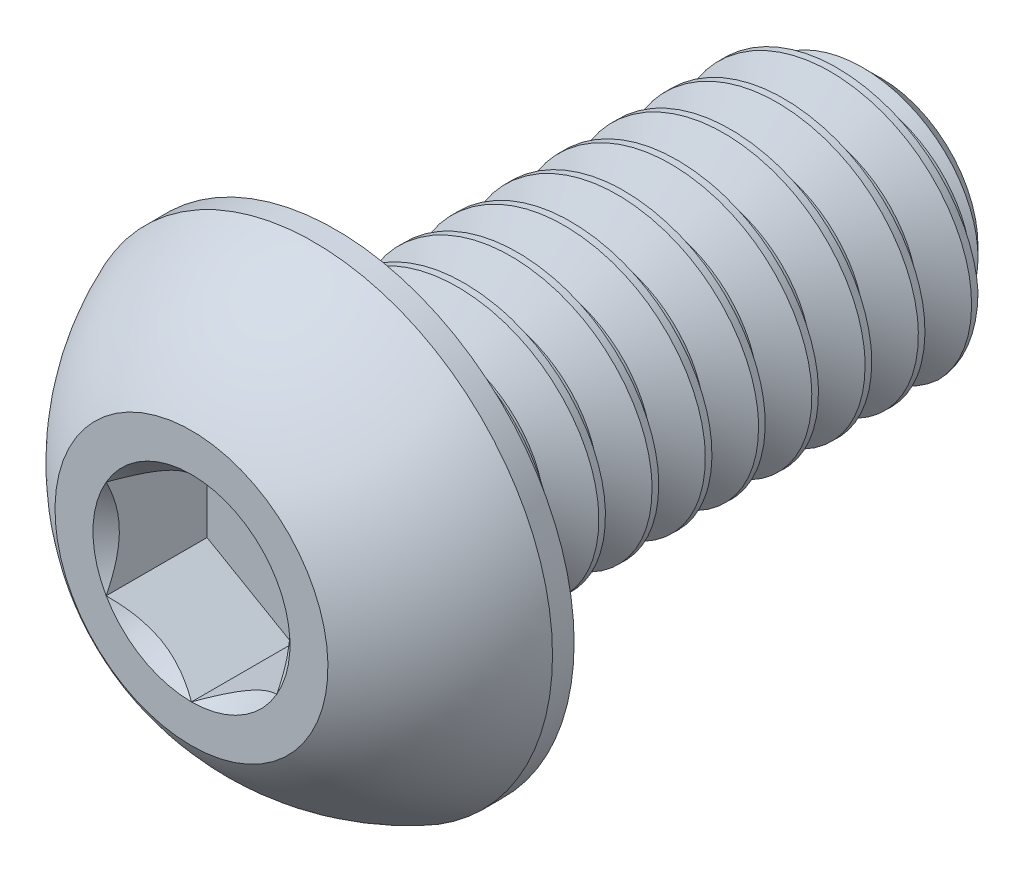
SolidWorks part; units mm, degrees
ref_plane "Front" through (0, 0, 0) normal (0, 0, 1) x (1, 0, 0)
ref_plane "Top" through (0, 0, 0) normal (0, 1, 0) x (1, 0, 0)
ref_plane "Right" through (0, 0, 0) normal (1, 0, 0) x (0, 0, -1)
sketch "Sketch1" plane through (0, 0, 0) normal (1, 0, 0) x (0, 0, -1)
  line L2 (3.3528, 3.175) -> (16.0528, 3.175)
  line L3 (16.0528, 3.175) -> (16.0528, 0)
  line L4 (16.0528, 0) -> (3.3528, 0)
  line L6 (2.8499, 5.5499) -> (3.3528, 5.5499) construction
  line L7 (16.0528, 3.175) -> (16.0528, -3.175) construction
  line L8 (0, 0) -> (3.3528, 0) construction
  line L9 (3.3528, 5.5499) -> (3.3528, -5.5499) construction
  line L11 (3.3528, 3.175) -> (3.3528, 0)
  line L13 (0, 1.9844) -> (0, -1.9844) construction
  line L14 (0, 1.9844) -> (0, 3.175) construction
  arc A3 (0, 3.175) -> (2.8499, 5.5499) centre (5.0603, 0) cw construction
  dimension "D1" = 0.5029
  dimension "Head Ht" = 3.3528
  dimension "Head Dia" = 11.0998
  dimension "Dia" = 6.35
  dimension "Lg" = 12.7
  dimension "Hex" = 3.9688
revolve "Revolve1" add sketch "Sketch1" angle 360 mid plane about L4
sketch "Sketch3" plane through (0, 0, -16.0528) normal (0, 0, -1) x (-1, 0, 0)
  circle A0 centre (0, 0) radius 3.175
curve "Helix/Spiral1" pitch 1.239 height 16.0528 radius 3.175 centre (0, 0, -16.0528) axis (0, 0, 1) start towards (0, 1, 0)
sketch "Sketch2" plane through (0, 0, 0) normal (1, 0, 0) x (0, 0, -1)
  line L0 (16.0528, 3.175) -> (17.1369, 3.175)
  line L1 (17.1369, 3.175) -> (16.6723, 2.3702)
  line L2 (16.6723, 2.3702) -> (16.5174, 2.3702)
  line L3 (16.5174, 2.3702) -> (16.0528, 3.175)
  line L4 (16.2851, 2.7726) -> (16.9046, 2.7726) construction
  dimension "D1" = 60
  dimension "D2" = 0.1549
  dimension "D3" = 0.6195
chamfer "Chamfer1" distance 0.9293 angle 45 1 edges at (0, 3.175, -16.0528)
sweep "Cut-Sweep1" cut profiles "Sketch2" path "Helix/Spiral1"
sketch "Sketch7" plane through (0, 0, 0) normal (1, 0, 0) x (0, 0, -1)
  line L6 (2.8499, 5.5499) -> (3.3528, 5.5499) construction
  line L8 (0, 0) -> (3.3528, 0) construction
  line L11 (3.3528, 5.5499) -> (3.3528, -5.5499) construction
  line L12 (2.8499, 5.5499) -> (3.3528, 5.5499)
  line L13 (0, 0) -> (3.3528, 0)
  line L14 (0, 1.9844) -> (0, -1.9844) construction
  line L15 (3.3528, 5.5499) -> (3.3528, 0)
  line L16 (0, 3.175) -> (0, 0)
  arc A2 (2.8499, 5.5499) -> (0, 3.175) centre (5.0603, 0) ccw construction
  arc A3 (2.8499, 5.5499) -> (0, 3.175) centre (5.0603, 0) ccw
revolve "Revolve2" add sketch "Sketch7" angle 360 mid plane about L13
sketch "Sketch5" plane through (0, 0, 0) normal (0, 0, 1) x (1, 0, 0)
  line L1 (1.9844, -1.1457) -> (1.9844, 1.1457)
  line L2 (1.9844, 1.1457) -> (0, 2.2914)
  line L3 (0, 2.2914) -> (-1.9844, 1.1457)
  line L4 (-1.9844, 1.1457) -> (-1.9844, -1.1457)
  line L5 (-1.9844, -1.1457) -> (0, -2.2914)
  line L6 (0, -2.2914) -> (1.9844, -1.1457)
  circle A0 centre (0, 0) radius 1.9844 construction
extrude "Cut-Extrude2" cut sketch "Sketch5" against normal blind 2.347
sketch "Sketch6" plane through (0, 0, 0) normal (0, 0, 1) x (1, 0, 0)
  circle A0 centre (0, 0) radius 2.2914
extrude "Cut-Extrude3" cut sketch "Sketch6" against normal blind 2.347 draft 45
sketch "Sketch9" [suppressed] plane through (0, 0, -3.3528) normal (0, 0, 1) x (1, 0, 0)
  circle A2 centre (0, 0) radius 3.175
extrude "Boss-Extrude2" [suppressed] add sketch "Sketch9" against normal offset from surface (76.2 mm away) 22.225 up to face at (0, 2.2457, -16.0528)
sketch "Sketch10" plane through (0, 0, 0) normal (1, 0, 0) x (0, 0, -1)
  line L0 (16.0528, 3.175) -> (16.0528, -3.175) construction
  point P0 (14.1943, -3.175)
  dimension "D1" = 1.8585
equation "\"D3@Helix/Spiral1\" = \"Lg@Sketch1\" + \"Head Ht@Sketch1\""
equation "\"D2@Sketch2\" = \"D4@Helix/Spiral1\" * .125"
equation "\"D3@Sketch2\" = \"D4@Helix/Spiral1\" * .5"
equation "\"D1@Chamfer1\" = \"D4@Helix/Spiral1\" * .75"
equation "\"D1@Cut-Extrude2\" = \"Head Ht@Sketch1\" * .7"
equation "\"D1@Sketch1\" = \"Head Ht@Sketch1\" * .15"
equation "\"D1@Sketch10\" = \"D4@Helix/Spiral1\" * 1.5"
equation "\"D1@Cut-Extrude3\" = \"D1@Cut-Extrude2\""
